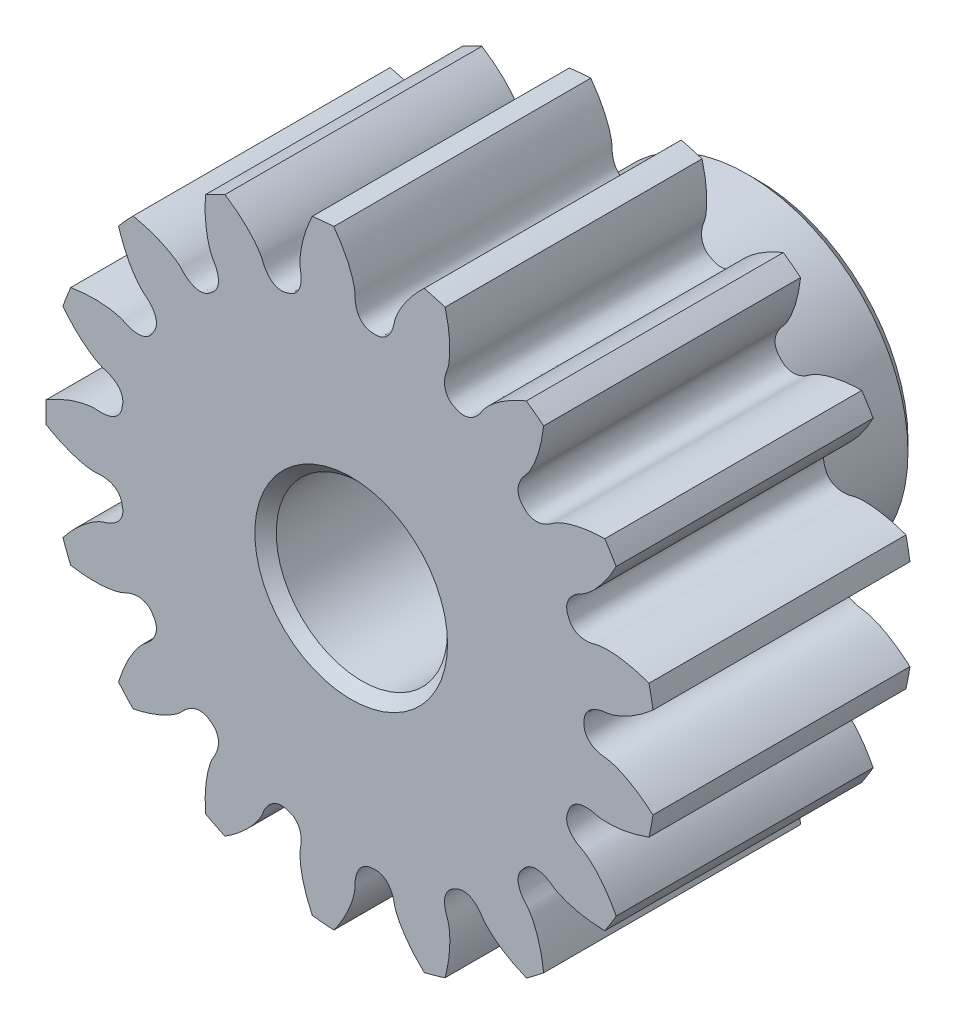
SolidWorks part; units mm, degrees
ref_plane "Front Plane" through (0, 0, 0) normal (0, 0, 1) x (1, 0, 0)
ref_plane "Top Plane" through (0, 0, 0) normal (0, 1, 0) x (1, 0, 0)
ref_plane "Right Plane" through (0, 0, 0) normal (1, 0, 0) x (0, 0, -1)
ref_axis "Axis1" through (0, 0, 55) along (0, 0, -1)
sketch "SketchRevolveSpur01" plane through (0, 0, 0) normal (1, 0, 0) x (0, 0, -1)
  line L0 (0, 0) -> (1, 0) construction
  line L1 (-6, 0) -> (-6, 14.25)
  line L2 (-6, 14.25) -> (6, 14.25)
  line L3 (6, 14.25) -> (6, 0)
  line L4 (6, 0) -> (-6, 0)
  dimension "Side1" = 6
  dimension "OutsideRadius" = 14.25
  dimension "Side2" = 6
revolve "Spur01" add sketch "SketchRevolveSpur01" angle 360 about L0
sketch "SketchToothSpur01" plane through (0, 0, 0) normal (0, 0, 1) x (1, 0, 0)
  arc A0 (14.1582, 2.1794) -> (14.1582, -2.1794) centre (0, 0) cw
  spline S0 degree 3 poles (14.1582, -2.1794) (14.0371, -2.0704) (13.8553, -1.9166) (13.6097, -1.7294) (13.4367, -1.6062) (13.2705, -1.4959) (13.1118, -1.3979) (12.9611, -1.3115) (12.819, -1.2361) (12.6861, -1.1711) (12.5628, -1.1157) (12.4497, -1.0693) (12.3473, -1.031) (12.2558, -1.0003) (12.1757, -0.9762) (12.1073, -0.9581) (12.0509, -0.9451) (12.0067, -0.9363) (11.892, -0.9179) (11.7642, -0.9101) (11.625, -0.8788) (11.5501, -0.8588) (11.4771, -0.835) (11.4058, -0.8073) (11.3359, -0.775) (11.2672, -0.7372) (11.1995, -0.6927) (11.1329, -0.64) (11.0681, -0.577) (11.0065, -0.5015) (10.9514, -0.4116) (10.907, -0.3068) (10.8816, -0.1962) (10.8729, -0.0924) (10.8759, 0) (10.8729, 0.0924) (10.8816, 0.1962) (10.907, 0.3068) (10.9514, 0.4116) (11.0065, 0.5015) (11.0681, 0.577) (11.1329, 0.64) (11.1995, 0.6927) (11.2672, 0.7372) (11.3359, 0.775) (11.4058, 0.8073) (11.4771, 0.835) (11.5501, 0.8588) (11.625, 0.8788) (11.7642, 0.9101) (11.892, 0.9179) (12.0067, 0.9363) (12.0509, 0.9451) (12.1073, 0.9581) (12.1757, 0.9762) (12.2558, 1.0003) (12.3473, 1.031) (12.4497, 1.0693) (12.5628, 1.1157) (12.6861, 1.1711) (12.819, 1.2361) (12.9611, 1.3115) (13.1118, 1.3979) (13.2705, 1.4959) (13.4367, 1.6062) (13.6097, 1.7294) (13.8553, 1.9166) (14.0371, 2.0704) (14.1582, 2.1794) knots 0 0 0 0 0.058708 0.085744 0.111236 0.135183 0.157584 0.178441 0.197753 0.21552 0.231742 0.246419 0.259551 0.271138 0.28118 0.289677 0.29663 0.302037 0.305899 0.338481 0.347946 0.357243 0.36643 0.375578 0.384778 0.39414 0.403802 0.413926 0.424699 0.43631 0.448916 0.462569 0.477143 0.489574 0.5 0.510426 0.522857 0.537431 0.551084 0.56369 0.575301 0.586074 0.596198 0.60586 0.615222 0.624422 0.63357 0.642757 0.652054 0.661519 0.694101 0.697963 0.70337 0.710323 0.71882 0.728862 0.740449 0.753581 0.768258 0.78448 0.802247 0.821559 0.842416 0.864817 0.888764 0.914256 0.941292 1 1 1 1
extrude "ToothExtrudeCutSpur01" cut sketch "SketchToothSpur01" against normal blind 6 and the other way blind 6
ref_axis "Axis2" through (15.7537, 0, 0) along (-1, 0, 0)
ref_plane "Plane1" through (0, 0, 0) normal (0, 0, -1) x (1, 0, 0)
pattern_circular "PatternSpur01" count 17 every 21.176 about axis through (0, 0, 55) along (0, 0, -1) of "ToothExtrudeCutSpur01"
sketch "HubSketchSide1" plane through (0, 0, 0) normal (1, 0, 0) x (0, 0, -1)
  line L0 (0, 0) -> (1, 0) construction
  line L1 (6.5, 7.5) -> (12.5, 7.5)
  line L2 (12.5, 7.5) -> (13, 7)
  line L3 (13, 7) -> (13, 0)
  line L4 (13, 0) -> (6, 0)
  line L5 (6, 0) -> (6, 8)
  arc A0 (6, 8) -> (6.5, 7.5) centre (6.5, 8) ccw
  dimension "HubFillet1" = 1
  dimension "HubRadius1" = 7.5
  dimension "HubChamferX1" = 0.5
  dimension "HubChamferY1" = 0.5
  dimension "HubFace1" = 13
  dimension "HubComponentFace1" = 6
revolve "HubRevolve1" add sketch "HubSketchSide1" angle 360 about L0
sketch "BoreRevolveSketch" plane through (0, 0, 0) normal (1, 0, 0) x (0, 0, -1)
  line L0 (0, 0) -> (1, 0) construction
  line L1 (-6, 0) -> (13, 0)
  line L2 (13, 0) -> (13, 4.5)
  line L3 (13, 4.5) -> (12.5, 4)
  line L4 (12.5, 4) -> (-5.5, 4)
  line L5 (-5.5, 4) -> (-6, 4.5)
  line L6 (-6, 4.5) -> (-6, 0)
  dimension "BoreSide1" = 13
  dimension "TaperSide1" = 4.5
  dimension "Chamfer1X" = 0.5
  dimension "Chamfer1Y" = 0.5
  dimension "BoreSide2" = 6
  dimension "TaperSide2" = 4.5
revolve "BoreRevolveCut" cut sketch "BoreRevolveSketch" angle 360 about L0
sketch "AuxiliarySketchSpur01" plane through (0, 0, 0) normal (0, 0, 1) x (1, 0, 0)
  circle A0 centre (0, 0) radius 12.75 construction
  circle A1 centre (0, 0) radius 11.9811 construction
  circle A2 centre (0, 0) radius 11.9811 construction
  circle A3 centre (0, 0) radius 14.25 construction
  circle A4 centre (0, 0) radius 10.875 construction
  dimension "PitchDiameter" = 25.5
  dimension "BaseDiameter" = 23.9622
  dimension "FormDiameter" = 23.9623
  dimension "MajorDiameter" = 28.5
  dimension "MinorDiameter" = 21.75
